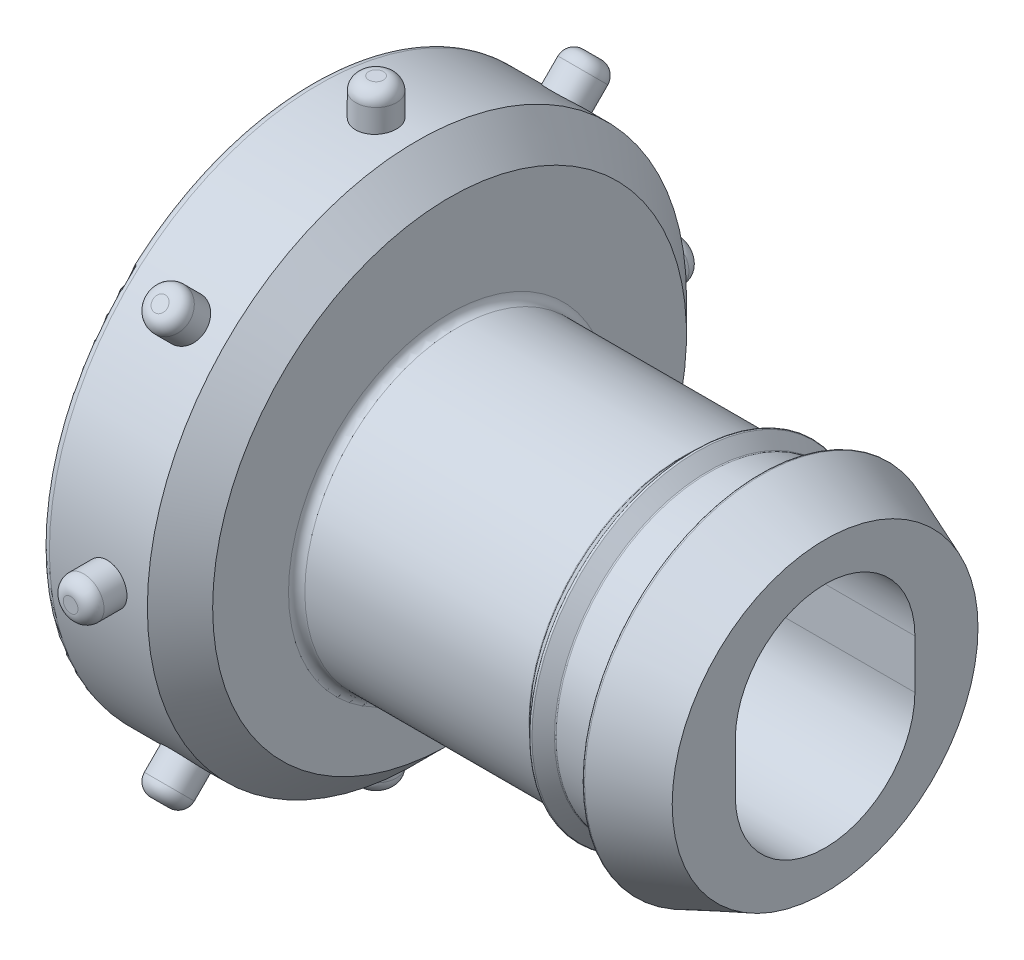
SolidWorks part; units mm, degrees
note: '?' marks a value the reader was unsure of. The reader was unsure of these and kept them because the rebuilt part matched: shared geometry of "Sketch2<3>".
ref_plane "Front Plane" through (0, 0, 0) normal (0, 0, 1) x (1, 0, 0)
ref_plane "Top Plane" through (0, 0, 0) normal (0, 1, 0) x (1, 0, 0)
ref_plane "Right Plane" through (0, 0, 0) normal (1, 0, 0) x (0, 0, -1)
sketch "Sketch1" plane through (0, 0, 0) normal (0, 1, 0) x (1, 0, 0)
  line L0 (0, 0) -> (-23, 0)
  line L1 (0, 0) -> (0, 9.365)
  line L2 (0, 9.365) -> (-3.97, 10.955)
  line L3 (-3.97, 10.955) -> (-3.97, 9.365)
  line L4 (0, 9.365) -> (-19.3321, 9.365) construction
  line L5 (-3.97, 9.365) -> (-7.15, 9.365)
  line L6 (-7.15, 9.365) -> (-7.94, 10.155)
  line L7 (-7.94, 10.155) -> (-8.73, 9.365)
  line L8 (-8.73, 9.365) -> (-23, 9.365)
  line L9 (-23, 9.365) -> (-23, 0)
  dimension "D1" = 23
  dimension "D2" = 9.365
  dimension "D3" = 1.59
  dimension "D4" = 3.97
  dimension "D5" = 7.94
  dimension "D6" = 0.79
revolve "Revolve1" add sketch "Sketch1" angle 360 about L0
sketch "Sketch2" plane through (-23, 0, 0) normal (-1, 0, 0) x (0, 0, 1)
  line L0 (0, 0) -> (0, 4.1864) construction
  line L1 (5.5, 1.5) -> (5.5, 0)
  line L3 (-5.5, 1.5) -> (-5.5, 0)
  line L4 (5.5, 0) -> (5.5, -1.5)
  line L5 (-5.5, -1.5) -> (-5.5, 0)
  circle A0 centre (0, 1.5) radius 9.365
  arc A1 (-5.5, 0) -> (-5.4486, -0.75) centre (0, 0) ccw
  circle A3 centre (0, 1.5) radius 16.51
  circle A4 centre (0, 0) radius 9.365 construction
  arc A6 (5.5, 1.5) -> (-5.5, 1.5) centre (0, 1.5) ccw
  arc A7 (-5.5, -1.5) -> (5.5, -1.5) centre (0, -1.5) ccw
  dimension "D1" = 11
  dimension "D2" = 33.02
  dimension "D3" = 1.5
  dimension "D4" = 1.5
extrude "Boss-Extrude1" add sketch "Sketch2" along normal blind 8.5
ref_axis "Axis1" through (-31.5, -17.1251, 0) along (0, 1, 0)?
sketch "Sketch4" plane through (-31.5, 0, 0) normal (-1, 0, 0) x (0, 0, 1)
  line L0 (0, -17.1251) -> (0, 19.1969) construction
  line L1 (9.09, 7.6298) -> (-9.09, 7.6298)
  line L2 (9.09, 7.6298) -> (9.09, -5.5702)
  line L3 (9.09, -5.5702) -> (-9.09, -5.5702)
  line L4 (-9.09, 7.6298) -> (-9.09, -5.5702)
  point P6 (0, 7.6298)
  dimension "D1" = 18.18
  dimension "D2" = 13.2
extrude "Cut-Extrude1" cut sketch "Sketch4" against normal blind 7
sketch "Sketch5" plane through (-31.5, 0, 0) normal (-1, 0, 0) x (0, 0, 1)
  line L0 (0, -17.1251) -> (0, 19.1969) construction
  circle A0 centre (0, 1.5) radius 14.14
  dimension "D1" = 28.28
  dimension "D2" = 1.5
sketch "Sketch6" plane through (0, 0, 0) normal (0, 0, 1) x (1, 0, 0)
  line L0 (-31.5, 15.64) -> (-31.5, -12.64) construction
  circle A0 centre (-31.5, 15.64) radius 0.9
  point P0 (-31.5, 15.64)
  dimension "D1" = 1.8
ref_axis "Axis2" through (-31.5, 1.5, 0) along (1, 0, 0)
revolve "Cut-Revolve1" cut sketch "Sketch6" angle 360 about axis through (-31.5, 1.5, 0) along (1, 0, 0)
ref_plane "Plane1" through (-27.5, 0, 0) normal (-1, 0, 0) x (0, 0, 1)
ref_axis "Axis3" through (-27.5, -18.3, 0) along (0, 1, 0)?
ref_plane "Plane2" through (0, 18.01, 0) normal (0, 1, 0) x (1, 0, 0)
sketch "Sketch7" plane through (0, 18.01, 0) normal (0, 1, 0) x (1, 0, 0)
  circle A0 centre (-27.5, 0) radius 1.25
  dimension "D1" = 2.5
extrude "Boss-Extrude2" add sketch "Sketch7" along normal blind 2.2 and the other way blind 2 contours A0
fillet "Fillet2" radius 0.8 1 edges at (-27.5, 20.21, 1.25)
pattern_circular "CirPattern1" count 8 over 360 about axis through (0, 1.5, 0) along (1, 0, 0) of "Boss-Extrude2", "Fillet2"
fillet "Fillet4" radius 0.1 5 edges at (-8.73, 0, -9.365) (-7.94, 0, -10.155) (-7.15, 0, -9.365) (-3.97, 0, -9.365) (-3.97, 0, -10.955)
extrude "Cut-Extrude2" cut sketch "Sketch2<3>" against normal through all both and the other way through all
sketch "Sketch2<3>" plane through (-23, 0, 0) normal (-1, 0, 0) x (0, 0, 1) same geometry as "Sketch2"
sketch "Sketch8" plane through (-24.5, 0, 0) normal (-1, 0, 0) x (0, 0, 1)
  line L0 (-5.5, 1.5) -> (-5.5, -1.5) construction
  line L1 (-9.09, -5.5702) -> (-5.5, -5.5702)
  line L2 (-9.09, -5.5702) -> (-9.09, 2.0798)
  line L3 (-9.09, 2.0798) -> (-5.5, 2.0798)
  line L4 (-5.5, -5.5702) -> (-5.5, 2.0798)
  line L9 (5.5, -1.5) -> (5.5, 1.5) construction
  line L13 (9.09, -5.5702) -> (5.5, -5.5702)
  line L14 (9.09, -5.5702) -> (9.09, 2.0798)
  line L15 (9.09, 2.0798) -> (5.5, 2.0798)
  line L16 (5.5, -5.5702) -> (5.5, 2.0798)
  dimension "D1" = 7.65
extrude "Boss-Extrude3" add sketch "Sketch8" along normal blind 0.64
fillet "Fillet5" radius 0.5 2 edges at (-25.14, 2.0798, 7.295) (-25.14, -1.7452, 5.5)
fillet "Fillet6" radius 0.5 1 edges at (-23, 0, 9.365)
chamfer "Chamfer1" distance 2 angle 45 1 edges at (-23, 1.5, 16.51)
fillet "Fillet7" radius 1 1 edges at (-31.5, 1.5, -13.24)
chamfer "Chamfer2" distance 1 distance2 6 1 edges at (-31.5, 7.6298, 0)
fillet "Fillet8" radius 0.5 1 edges at (-31.5, 1.5, 16.51)
equation "\"WallThick\"= 1.2'thickness of wall for printer"
equation "\"dHole\"= 3.3'diameter of screw hole"
equation "\"D1@Boss-Extrude2\"=(37.42-33.02)/2"
